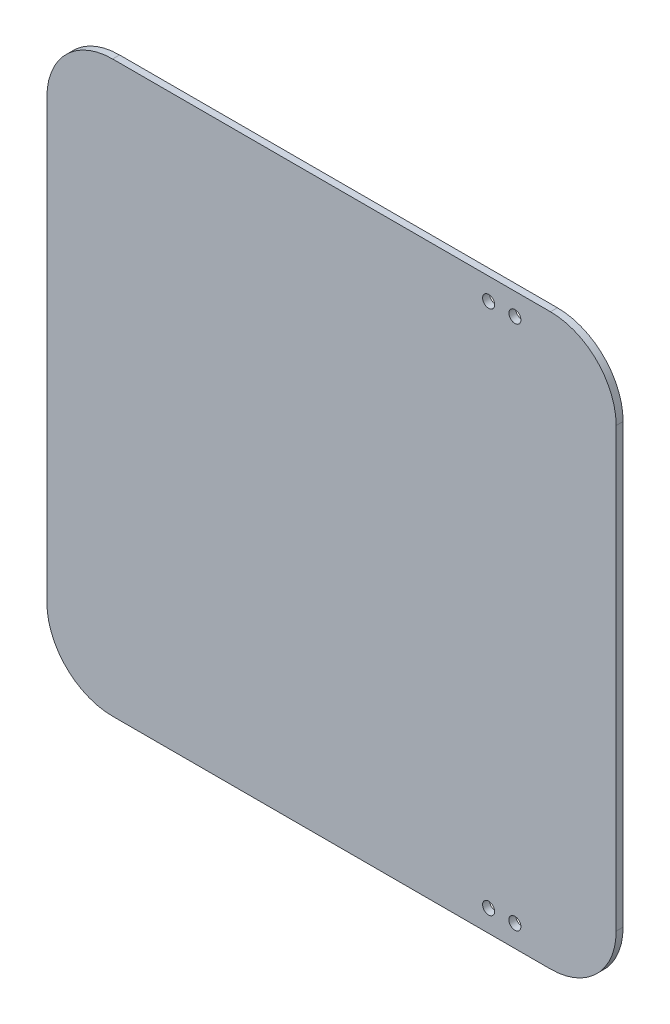
SolidWorks part; units mm, degrees
ref_plane "Front Plane" through (0, 0, 0) normal (0, 0, 1) x (1, 0, 0)
ref_plane "Top Plane" through (0, 0, 0) normal (0, 1, 0) x (1, 0, 0)
ref_plane "Right Plane" through (0, 0, 0) normal (1, 0, 0) x (0, 0, -1)
sketch "Sketch1" plane through (0, 0, 0) normal (0, 0, 1) x (1, 0, 0)
  line L4 (79.7168, 314.2679) -> (-120.2832, 314.2679)
  line L5 (109.7168, 84.2679) -> (109.7168, 284.2679)
  line L6 (-120.2832, 54.2679) -> (79.7168, 54.2679)
  line L7 (-150.2832, 284.2679) -> (-150.2832, 84.2679)
  arc A4 (-120.2832, 314.2679) -> (-150.2832, 284.2679) centre (-120.2832, 284.2679) ccw
  arc A5 (109.7168, 284.2679) -> (79.7168, 314.2679) centre (79.7168, 284.2679) ccw
  arc A6 (79.7168, 54.2679) -> (109.7168, 84.2679) centre (79.7168, 84.2679) ccw
  arc A7 (-150.2832, 84.2679) -> (-120.2832, 54.2679) centre (-120.2832, 84.2679) ccw
extrude "Boss-Extrude1" add sketch "Sketch1" against normal blind 3.175 contours L4 A4 L7 A7 L6 A6 L5 A5
sketch "Sketch2" plane through (0, 0, 0) normal (0, 0, 1) x (1, 0, 0)
  circle A0 centre (51.4668, 304.2679) radius 2.75 construction
  circle A1 centre (63.4668, 304.2679) radius 2.75 construction
  circle A2 centre (51.4668, 304.2679) radius 2.75
  circle A3 centre (63.4668, 304.2679) radius 2.75
  circle A4 centre (63.4668, 64.2679) radius 2.75 construction
  circle A5 centre (51.4668, 64.2679) radius 2.75 construction
  circle A6 centre (63.4668, 64.2679) radius 2.75
  circle A7 centre (51.4668, 64.2679) radius 2.75
extrude "Cut-Extrude1" cut sketch "Sketch2" against normal through all
